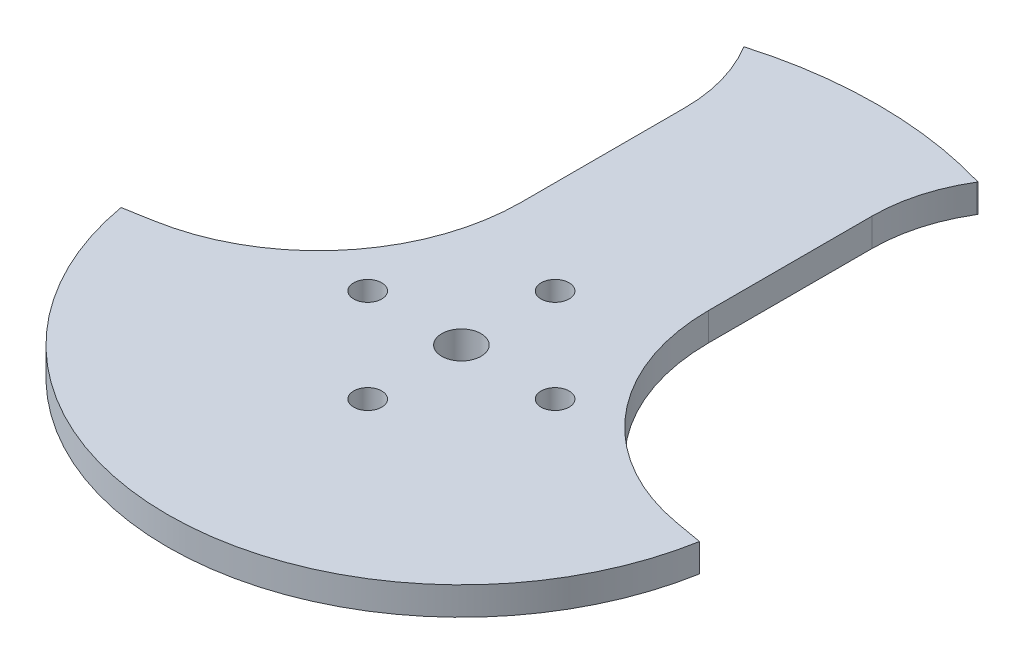
SolidWorks part; units mm, degrees
material "Cast Alloy Steel"
ref_plane "Front Plane" through (0, 0, 0) normal (0, 0, 1) x (1, 0, 0)
ref_plane "Top Plane" through (0, 0, 0) normal (0, 1, 0) x (1, 0, 0)
ref_plane "Right Plane" through (0, 0, 0) normal (1, 0, 0) x (0, 0, -1)
other "Center of Mass"
ref_axis "Axis1" through (0, -55, 0) along (0, 1, 0)
sketch "Sketch1" plane through (0, 0, 0) normal (0, 1, 0) x (1, 0, 0)
  line L0 (-12.5, 42.6562) -> (-12.448, 42.5708)
  line L1 (-12.5, 42.6562) -> (0, 0) construction
  line L2 (0, -1000) -> (0, 49000) construction
  line L3 (-10, 33.8421) -> (-10, 16.409)
  line L4 (12.5, 42.6562) -> (12.448, 42.5708)
  line L5 (10, 33.8421) -> (10, 16.409)
  line L6 (0, 0) -> (-43.7747, -7.7187) construction
  line L7 (-27.8962, -4.9188) -> (-30.8737, -5.4439)
  line L8 (27.8962, -4.9188) -> (30.8737, -5.4439)
  line L9 (-1000, 0) -> (49000, 0) construction
  circle A0 centre (0, 0) radius 44.45 construction
  arc A1 (-12.5, 42.6562) -> (12.5, 42.6562) centre (0, 0) cw
  arc A2 (-12.448, 42.5708) -> (-10, 33.8421) centre (-26.7857, 33.8421) cw
  arc A3 (12.448, 42.5708) -> (10, 33.8421) centre (26.7857, 33.8421) ccw
  arc A4 (-10, 16.409) -> (-27.8962, -4.9188) centre (-31.6569, 16.409) cw
  arc A5 (-30.8737, -5.4439) -> (30.8737, -5.4439) centre (0, 0) ccw
  arc A6 (10, 16.409) -> (27.8962, -4.9188) centre (31.6569, 16.409) ccw
  circle A7 centre (0, 0) radius 31.35 construction
  circle A8 centre (0, 0) radius 14 construction
  dimension "D1" = 88.9
  dimension "D7" = 62.7
  dimension "D9" = 28
  dimension "D2" = 15
  dimension "D3" = 0.1
  dimension "D4" = 20
  dimension "D5" = 25
  dimension "D6" = 80
extrude "Boss-Extrude1" add sketch "Sketch1" along normal blind 3
sketch "Sketch2" plane through (0, 3, 0) normal (0, 1, 0) x (1, 0, 0)
  line L0 (0, -201000) -> (0, 249000) construction
  circle A0 centre (0, 0.0141) radius 2.1
  circle A1 centre (0, 0.0141) radius 10 construction
  circle A2 centre (10, 0.0141) radius 1.5
  circle A3 centre (0, 10.0141) radius 1.5
  circle A4 centre (-10, 0.0141) radius 1.5
  circle A5 centre (0, -9.9859) radius 1.5
  point P0 (0, 0.0141)
  dimension "D1" = 4.2
  dimension "D2" = 3
  dimension "D3" = 20
extrude "Cut-Extrude1" cut sketch "Sketch2" against normal through all
